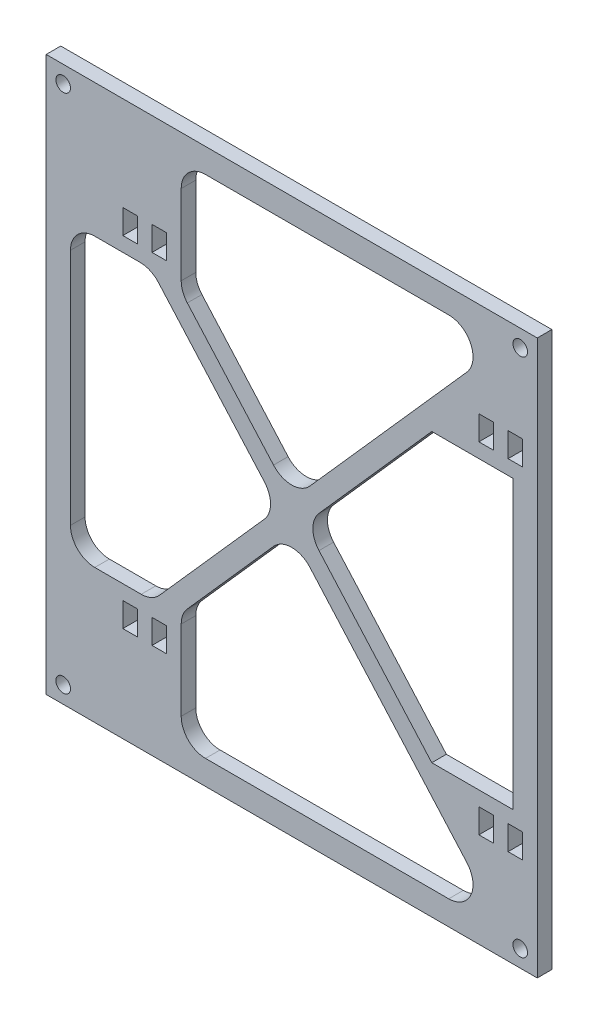
SolidWorks part; units mm, degrees
ref_plane "Front Plane" through (0, 0, 0) normal (0, 0, 1) x (1, 0, 0)
ref_plane "Top Plane" through (0, 0, 0) normal (0, 1, 0) x (1, 0, 0)
ref_plane "Right Plane" through (0, 0, 0) normal (1, 0, 0) x (0, 0, -1)
sketch "Sketch1" plane through (0, 0, 0) normal (0, 0, 1) x (1, 0, 0)
  line L0 (71.6864, -54.1061) -> (71.6572, -54.0732)
  line L1 (71.6864, 56.8779) -> (-29.3136, 56.8779)
  line L2 (71.6864, 56.8779) -> (71.6864, -57.1221)
  line L3 (71.6864, -57.1221) -> (-29.3136, -57.1221)
  line L4 (-29.3136, 56.8779) -> (-29.3136, -57.1221)
  line L5 (71.6864, 56.8779) -> (-29.3136, -57.1221) construction
  line L6 (71.6864, -57.1221) -> (-29.3136, 56.8779) construction
  line L7 (-11.1018, -52.1221) -> (53.4747, -52.1221)
  line L8 (-24.3136, -35.2791) -> (-24.3136, 35.035)
  line L9 (-11.1018, 51.8779) -> (53.4747, 51.8779)
  line L10 (66.6864, -35.2791) -> (66.6864, 35.035)
  line L11 (-23.7247, -50.8138) -> (66.0975, 50.5697) construction
  line L12 (-23.7247, 50.5697) -> (66.0975, -50.8138) construction
  line L13 (69.0144, 56.8779) -> (68.9414, 56.7956)
  line L14 (69.0144, -57.1221) -> (68.9414, -57.0397)
  line L15 (71.6864, 53.862) -> (71.6572, 53.829)
  line L16 (73.1834, 55.5517) -> (-27.8166, -58.4483) construction
  line L17 (70.1894, 58.2042) -> (-30.8106, -55.7958) construction
  line L18 (57.9439, 38.3507) -> (26.796, 3.1936)
  line L19 (57.2172, 43.5622) -> (24.9289, 7.1181)
  line L20 (17.4439, -7.3622) -> (-14.8443, -43.8064)
  line L21 (17.4439, 7.1181) -> (-14.8443, 43.5622)
  line L22 (73.1834, -55.7958) -> (-27.8166, 58.2042) construction
  line L23 (15.5768, -3.4378) -> (-15.5711, -38.5948)
  line L24 (15.5768, 3.1936) -> (-15.5711, 38.3507)
  line L25 (70.1894, -58.4483) -> (-30.8106, 55.5517) construction
  line L26 (57.9439, -38.5948) -> (26.796, -3.4378)
  line L27 (57.2172, -43.8064) -> (24.9289, -7.3622)
  line L28 (-26.5685, -57.0397) -> (-26.6415, -57.1221)
  line L29 (-29.2844, -54.0732) -> (-29.3136, -54.1061)
  circle A0 centre (68.1864, 53.3779) radius 1.5
  circle A1 centre (68.1864, -53.6221) radius 1.5
  circle A2 centre (-25.8136, -53.6221) radius 1.5
  circle A3 centre (-25.8136, 53.3779) radius 1.5
  circle A4 centre (-25.8136, 53.3779) radius 3.5 construction
  circle A5 centre (-25.8136, -53.6221) radius 3.5 construction
  circle A6 centre (68.1864, -53.6221) radius 3.5 construction
  circle A7 centre (68.1864, 53.3779) radius 3.5 construction
  arc A9 (15.5768, 3.1936) -> (15.5768, -3.4378) centre (11.8343, -0.1221) cw
  arc A10 (17.4439, -7.3622) -> (24.9289, -7.3622) centre (21.1864, -10.6779) cw
  arc A11 (26.796, -3.4378) -> (26.796, 3.1936) centre (30.5385, -0.1221) cw
  arc A12 (24.9289, 7.1181) -> (17.4439, 7.1181) centre (21.1864, 10.4338) cw
  arc A13 (-11.1018, 51.8779) -> (-14.8443, 43.5622) centre (-11.1018, 46.8779) ccw
  arc A14 (-15.5711, 38.3507) -> (-24.3136, 35.035) centre (-19.3136, 35.035) ccw
  arc A15 (-15.5711, -38.5948) -> (-24.3136, -35.2791) centre (-19.3136, -35.2791) cw
  arc A16 (-14.8443, -43.8064) -> (-11.1018, -52.1221) centre (-11.1018, -47.1221) ccw
  arc A17 (57.2172, -43.8064) -> (53.4747, -52.1221) centre (53.4747, -47.1221) cw
  arc A18 (66.6864, -35.2791) -> (57.9439, -38.5948) centre (61.6864, -35.2791) cw
  arc A19 (66.6864, 35.035) -> (57.9439, 38.3507) centre (61.6864, 35.035) ccw
  arc A20 (57.2172, 43.5622) -> (53.4747, 51.8779) centre (53.4747, 46.8779) ccw
  point P0 (21.1864, -0.1221)
  point P6 (21.1864, -0.1221)
  point P67 (18.5144, -0.1221)
  point P84 (64.5846, -52.1221)
  point P87 (66.6864, -48.4625)
  dimension "D4" = 5
  dimension "D1" = 2
  dimension "D2" = 2
  dimension "D3" = 2
extrude "Boss-Extrude1" add sketch "Sketch1" along normal blind 3 contours L1 L4 L3 L2 A20 L19 A12 L21 A13 L9 A19 L10 A18 L26 A11 L18 L23 A15 L8 A14 L24 A9 A3 A2 A1 A0 region at (21.1864, -0.1221, 0)
sketch "Sketch2" plane through (0, 0, 3) normal (0, 0, 1) x (1, 0, 0)
  line L0 (66.6864, -35.2791) -> (66.6864, 35.035) construction
  line L1 (65.6864, 37.3779) -> (68.6864, 37.3779)
  line L2 (65.6864, 37.3779) -> (65.6864, 32.3779)
  line L3 (65.6864, 32.3779) -> (68.6864, 32.3779)
  line L4 (68.6864, 37.3779) -> (68.6864, 32.3779)
  line L5 (70.0993, 29.3779) -> (49.9944, 29.3779)
  line L6 (57.9439, 38.3507) -> (26.796, 3.1936) construction
  line L7 (69.75, -29.6221) -> (49.9944, -29.6221)
  line L8 (57.9439, -38.5948) -> (26.796, -3.4378) construction
  line L9 (71.6864, 56.8779) -> (71.6864, -57.1221) construction
  line L10 (59.6864, 37.3779) -> (62.6864, 37.3779)
  line L11 (59.6864, 37.3779) -> (59.6864, 32.3779)
  line L12 (62.6864, 37.3779) -> (62.6864, 32.3779)
  line L13 (59.6864, 32.3779) -> (62.6864, 32.3779)
  line L14 (65.6864, -32.6221) -> (68.6864, -32.6221)
  line L15 (65.6864, -32.6221) -> (65.6864, -37.6221)
  line L16 (65.6864, -37.6221) -> (68.6864, -37.6221)
  line L17 (68.6864, -32.6221) -> (68.6864, -37.6221)
  line L18 (59.6864, -32.6221) -> (62.6864, -32.6221)
  line L19 (59.6864, -32.6221) -> (59.6864, -37.6221)
  line L20 (62.6864, -32.6221) -> (62.6864, -37.6221)
  line L21 (59.6864, -37.6221) -> (62.6864, -37.6221)
  line L22 (61.1864, 32.3779) -> (61.1864, -32.6221) construction
  line L23 (66.6864, -0.1221) -> (61.1864, -0.1221) construction
  line L24 (49.9944, -29.6221) -> (69.75, -51.9204)
  line L25 (69.75, -51.9204) -> (69.75, -29.6221)
  line L26 (49.9944, 29.3779) -> (70.0993, 52.7452)
  line L27 (70.0993, 52.7452) -> (70.0993, 29.3779)
  arc A0 (57.9439, -38.5948) -> (66.6864, -35.2791) centre (61.6864, -35.2791) ccw construction
  arc M27 (57.9439, 38.3507) -> (66.6864, 35.035) centre (61.6864, 35.035) cw
  line M28 (66.6864, 35.035) -> (66.6864, -35.2791)
  dimension "D1" = 3
  dimension "D2" = 5
  dimension "D3" = 3
  dimension "D6" = 65
  dimension "D7" = 3
  dimension "D8" = 3
  dimension "D9" = 3
  dimension "D4" = 2
  dimension "D5" = 2
extrude "Boss-Extrude2" add sketch "Sketch2" against normal blind 3
extrude "Cut-Extrude1" cut sketch "Sketch2<2>" against normal blind 3 contours L4 L1 L3 M27 M28 | L17 L16 L15 L14 region at (67.6365, 34.9596, 3)
sketch "Sketch2<2>" plane through (0, 0, 3) normal (0, 0, 1) x (1, 0, 0) same geometry as "Sketch2"
sketch "Sketch3" plane through (0, 0, 3) normal (0, 0, 1) x (1, 0, 0)
  line L0 (-13.5418, -32.5) -> (-10.5418, -32.5)
  line L9 (-13.5418, -32.5) -> (-13.5418, -37.5)
  line L10 (-13.5418, -37.5) -> (-10.5418, -37.5)
  line L11 (-10.5418, -32.5) -> (-10.5418, -37.5)
  line L12 (-7.5418, -32.5) -> (-4.5418, -32.5)
  line L13 (-7.5418, -32.5) -> (-7.5418, -37.5)
  line L14 (-7.5418, -37.5) -> (-4.5418, -37.5)
  line L15 (-4.5418, -32.5) -> (-4.5418, -37.5)
  line L17 (-4.5418, -37.5) -> (-4.5418, -32.5) construction
  line L18 (-1.5418, -27.0048) -> (-1.5418, -52.1221)
  line L20 (-11.1018, -52.1221) -> (53.4747, -52.1221) construction
  line L21 (-7.5134, -29.5) -> (-24.3136, -29.5)
  line L22 (15.5768, -3.4378) -> (-15.5711, -38.5948) construction
  line L23 (-24.3136, -35.2791) -> (-24.3136, 35.035) construction
  line L24 (-1.5418, -27.0048) -> (-7.5134, -29.5)
  line L25 (-24.3136, -29.5) -> (-24.3136, -52.1221)
  line L26 (-24.3136, -52.1221) -> (-1.5418, -52.1221)
  dimension "D1" = 32.5
  dimension "D2" = 3
  dimension "D3" = 5
  dimension "D6" = 3
  dimension "D7" = 3
  dimension "D4" = 3
extrude "Boss-Extrude3" add sketch "Sketch3" against normal blind 3
extrude "Cut-Extrude2" cut sketch "Sketch3<2>" against normal blind 3 contours L11 L10 L9 L0 | L13 L14 L15 L12
sketch "Sketch3<2>" plane through (0, 0, 3) normal (0, 0, 1) x (1, 0, 0) same geometry as "Sketch3"
mirror "Mirror1" about plane through (0, 0, 0) normal (0, 1, 0) of "Boss-Extrude3", "Cut-Extrude2"
fillet "Fillet4" radius 5 8 edges at (-7.5134, -29.5, 1.5) (-24.3136, -29.5, 1.5) (-1.5418, -52.1221, 1.5) (-1.5418, -28.7917, 1.5) (-1.5418, 51.8779, 1.5) (-1.5418, 28.5476, 1.5) (-24.3136, 29.5, 1.5) (-7.7297, 29.5, 1.5)
